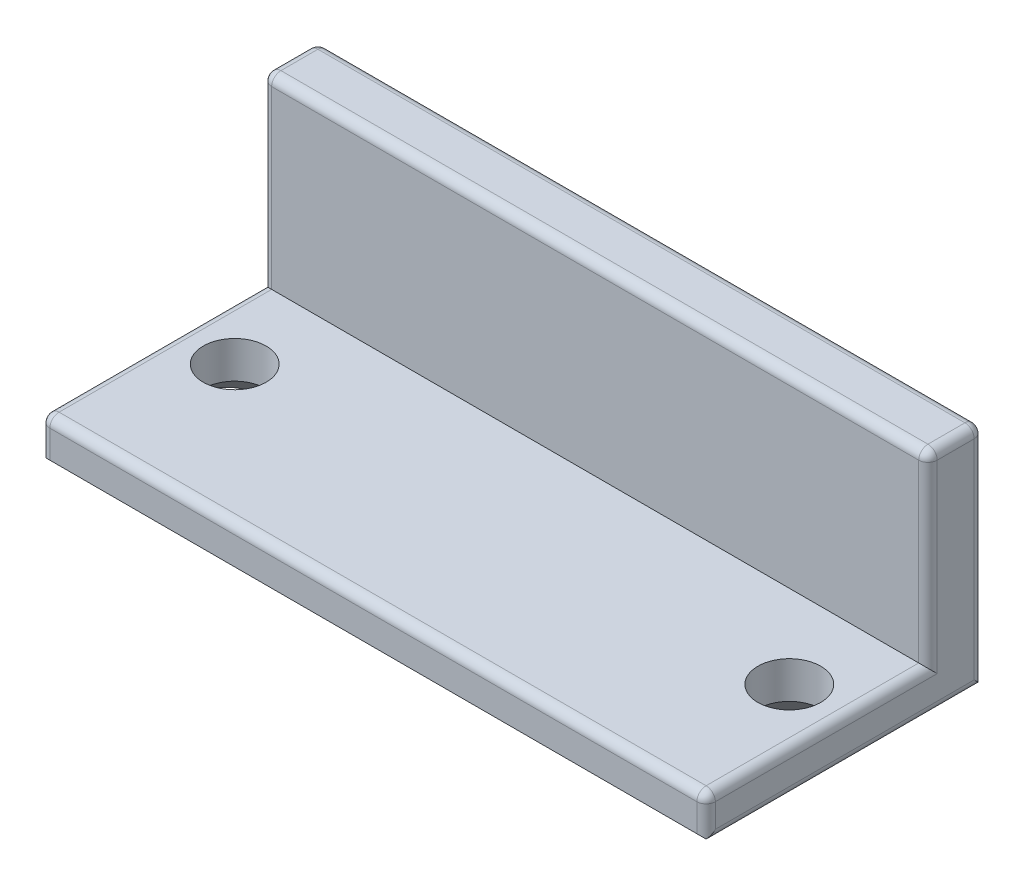
SolidWorks part; units mm, degrees
ref_plane "Спереди" through (0, 0, 0) normal (0, 0, 1) x (1, 0, 0)
ref_plane "Сверху" through (0, 0, 0) normal (0, 1, 0) x (1, 0, 0)
ref_plane "Справа" through (0, 0, 0) normal (1, 0, 0) x (0, 0, -1)
sketch "Эскиз1" plane through (0, 0, 0) normal (0, 1, 0) x (1, 0, 0)
  line L1 (-18, -7.5) -> (18, -7.5)
  line L2 (-18, -7.5) -> (-18, 7.5)
  line L3 (-18, 7.5) -> (18, 7.5)
  line L4 (18, -7.5) -> (18, 7.5)
  line L5 (0, 7.5) -> (0, -7.5) construction
  line L6 (-18, 0) -> (18, 0) construction
  point P0 (0, 0)
  dimension "D1" = 36
  dimension "D2" = 15
extrude "Бобышка-Вытянуть1" add sketch "Эскиз1" along normal blind 4
sketch "Эскиз2" plane through (0, 4, 0) normal (0, 1, 0) x (1, 0, 0)
  line L0 (18, -7.5) -> (18, 7.5) construction
  line L1 (-18, 7.5) -> (18, 7.5)
  line L2 (-18, 7.5) -> (-18, 4.5)
  line L3 (-18, 4.5) -> (18, 4.5)
  line L4 (18, 7.5) -> (18, 4.5)
  dimension "D1" = 3
extrude "Бобышка-Вытянуть2" add sketch "Эскиз2" along normal blind 10
sketch "Эскиз3" plane through (0, 0, 0) normal (0, -1, 0) x (1, 0, 0)
  line L0 (-18, 0) -> (18, 0) construction
  line L1 (-18, -7.5) -> (-18, 7.5) construction
  line L2 (18, 7.5) -> (18, -7.5) construction
  line L3 (0, 9.5274) -> (0, -7.5) construction
  line L4 (18, -7.5) -> (-18, -7.5) construction
  circle A0 centre (15, 0) radius 1.7
  circle A1 centre (-15, 0) radius 1.7
  dimension "D1" = 3.4
  dimension "D2" = 30
extrude "Вырез-Вытянуть1" cut sketch "Эскиз3" against normal blind 8
chamfer "Фаска1" distance 2 angle 45 6 edges at (0, 0, -7.5) (-18, 0, 0) (0, 0, 7.5) (18, 0, 0) (-15, 0, 1.7) (15, 0, -1.7)
fillet "Скругление1" radius 0.5 14 edges at (-18, 9, -4.5) (-18, 4, 1.5) (-18, 3, 7.5) (-18, 2, 0) (-18, 8, -7.5) (0, 14, -7.5) (0, 14, -4.5) (-18, 14, -6) (18, 4, 1.5) (18, 9, -4.5) (18, 14, -6) (18, 8, -7.5) (18, 2, 0) (18, 3, 7.5)
fillet "Скругление2" radius 0.5 3 edges at (-17.8536, 3.8536, 7.3536) (17.8536, 3.8536, 7.3536) (0, 4, 7.5)
